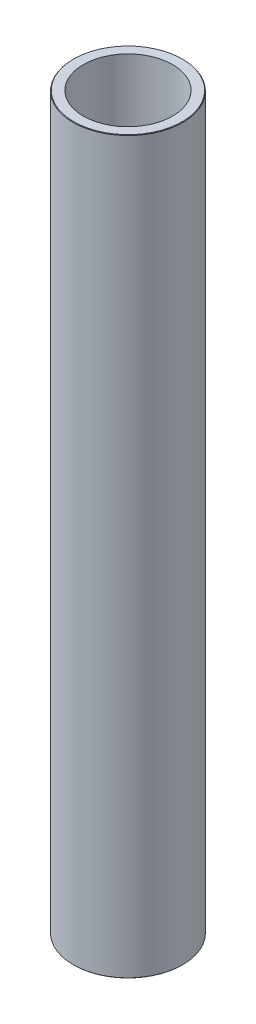
SolidWorks part; units mm, degrees
ref_plane "Front Plane" through (0, 0, 0) normal (0, 0, 1) x (1, 0, 0)
ref_plane "Top Plane" through (0, 0, 0) normal (0, 1, 0) x (1, 0, 0)
ref_plane "Right Plane" through (0, 0, 0) normal (1, 0, 0) x (0, 0, -1)
sketch "Sketch1" plane through (0, 0, 0) normal (0, 1, 0) x (1, 0, 0)
  circle A0 centre (0, 0) radius 45
  dimension "SHAFT_OD" = 90
extrude "Boss-Extrude1" add sketch "Sketch1" along normal blind 600
sketch "Sketch2" plane through (0, 0, 0) normal (0, 1, 0) x (1, 0, 0)
  circle A0 centre (0, 0) radius 36.6763
  dimension "BORE_D" = 73.3527
extrude "Cut-Extrude1" cut sketch "Sketch2" along normal through all
chamfer "Chamfer1" distance 0.3945 angle 45 2 edges at (0, 600, 45) (0, 0, 45)
